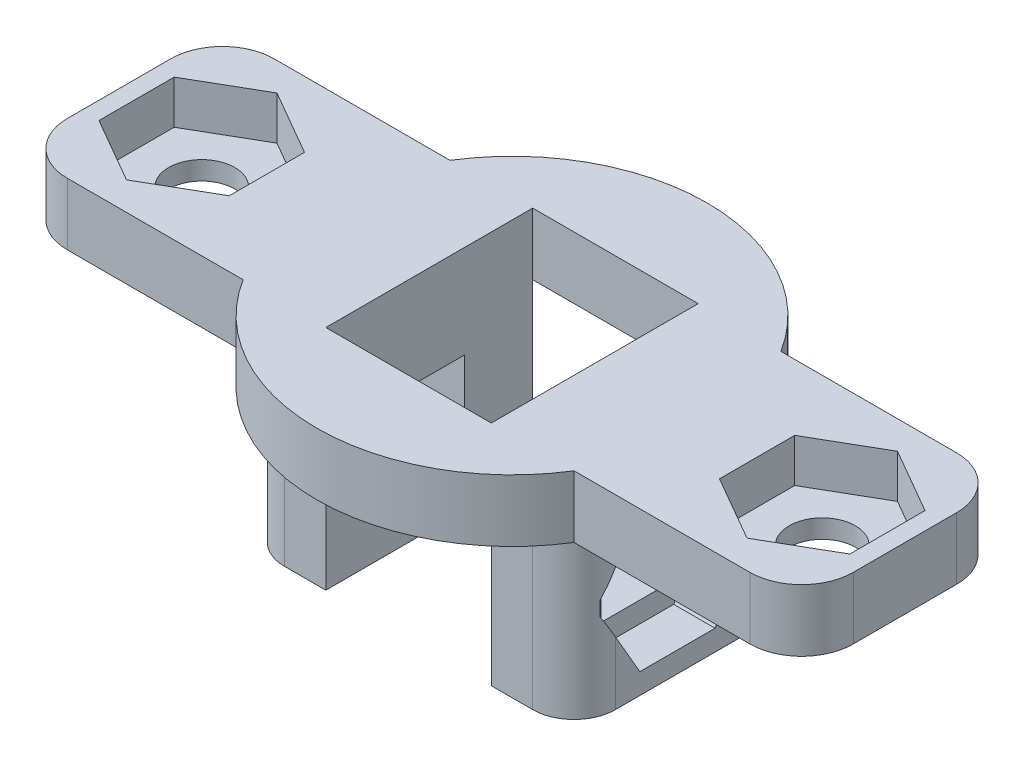
SolidWorks part; units mm, degrees
ref_plane "Front Plane" through (0, 0, 0) normal (0, 0, 1) x (1, 0, 0)
ref_plane "Top Plane" through (0, 0, 0) normal (0, 1, 0) x (1, 0, 0)
ref_plane "Right Plane" through (0, 0, 0) normal (1, 0, 0) x (0, 0, -1)
sketch "Sketch1" plane through (0, 0, 0) normal (0, 1, 0) x (1, 0, 0)
  line L0 (-19, 10) -> (-19, 0) construction
  line L1 (-38, 10) -> (0, 10)
  line L2 (-38, 10) -> (-38, 0)
  line L3 (-38, 0) -> (0, 0)
  line L4 (0, 10) -> (0, 0)
  line L9 (-27, 10) -> (-23, 10)
  line L10 (-27, 10) -> (-27, 0)
  line L11 (-27, 0) -> (-23, 0)
  line L12 (-23, 10) -> (-23, 0)
  line L13 (-15, 10) -> (-11, 10)
  line L14 (-15, 10) -> (-15, 0)
  line L15 (-15, 0) -> (-11, 0)
  line L16 (-11, 10) -> (-11, 0)
  line L17 (-32.5, 9) -> (-32.5, 10) construction
  line L18 (-38, 9) -> (-27, 9)
  line L19 (-38, 9) -> (-38, 1)
  line L20 (-38, 1) -> (-27, 1)
  line L21 (-27, 9) -> (-27, 1)
  line L22 (-32.5, 1) -> (-32.5, 0) construction
  arc A0 (-27, 0) -> (-11, 0) centre (-19, 5) ccw
  arc A1 (-11, 10) -> (-27, 10) centre (-19, 5) ccw
  dimension "D1" = 4
  dimension "D2" = 4
  dimension "D3" = 4
  dimension "D4" = 38
  dimension "D5" = 10
  dimension "D6" = 4
  dimension "D7" = 8
extrude "Boss-Extrude1" add sketch "Sketch1" along normal blind 3 contours L2 L20 L10 L18 | L12 L1 L10 L3 | L1 A1 | L16 L1 L14 L3 | L3 A0 | L1 L16 L3 L4 | L2 L18 L10 L1 | L20 L2 L3 L10 region at (-32.5, 0, -9.5) region at (-19, 0, -11.815) region at (-25, 0, -5) region at (-32.5, 0, -5) region at (-13, 0, -5) region at (-5.5, 0, -5) region at (-32.5, 0, -0.5) region at (-19, 0, 1.815)
extrude "Boss-Extrude2" add sketch "Sketch1<3>" against normal blind 8 contours L12 L1 L10 L3 | L16 L1 L14 L3 region at (-25, 0, -5) region at (-13, 0, -5)
sketch "Sketch1<3>" plane through (0, 0, 0) normal (0, 1, 0) x (1, 0, 0) same geometry as "Sketch1"
sketch "Sketch3" plane through (0, 3, 0) normal (0, 1, 0) x (1, 0, 0)
  line L0 (-38, 5) -> (0, 5) construction
  line L1 (-38, 10) -> (-38, 0) construction
  line L2 (0, 10) -> (0, 0) construction
  line L3 (-38, 10) -> (-38, 0) construction
  line L4 (-7.15, 6.8187) -> (-7.15, 3.1813)
  line L5 (-7.15, 3.1813) -> (-4, 1.3627)
  line L6 (-4, 1.3627) -> (-0.85, 3.1813)
  line L7 (-0.85, 3.1813) -> (-0.85, 6.8187)
  line L8 (-0.85, 6.8187) -> (-4, 8.6373)
  line L9 (-4, 8.6373) -> (-7.15, 6.8187)
  line L10 (-30.85, 3.1813) -> (-30.85, 6.8187)
  line L11 (-30.85, 6.8187) -> (-34, 8.6373)
  line L12 (-34, 8.6373) -> (-37.15, 6.8187)
  line L13 (-37.15, 6.8187) -> (-37.15, 3.1813)
  line L14 (-37.15, 3.1813) -> (-34, 1.3627)
  line L15 (-34, 1.3627) -> (-30.85, 3.1813)
  circle A0 centre (-4, 5) radius 3.15 construction
  circle A1 centre (-34, 5) radius 3.15 construction
  point P0 (-34, 5)
  point P1 (-4, 5)
  point P12 (-19, 5)
  dimension "D3" = 6.3
  dimension "D4" = 6.3
  dimension "D1" = 15
  dimension "D2" = 15
extrude "Cut-Extrude5" cut sketch "Sketch3" against normal blind 2.1
hole_wizard "Hole1" positions "3DSketch1" profile "Sketch8" legacy end condition through all
sketch3d "3DSketch1"
  point P0 (-4, 3, -5)
  point P3 (-34, 3, -5)
sketch "Sketch8" plane through (-4, 3, -5) normal (1, 0, 0) x (0, 0, 1)
  line L0 (0, 0) -> (0, 11)
  line L1 (0, 11) -> (1.6, 11)
  line L2 (1.6, 11) -> (1.6, 0)
  line L3 (1.6, 0) -> (0, 0)
  line L4 (0, 110) -> (0, -10) construction
  dimension "Diameter" = 3.2
  dimension "Depth" = 11
sketch "Sketch5" plane through (-27, 0, 0) normal (-1, 0, 0) x (0, 0, 1)
  line L0 (-5, 0) -> (-5, -8) construction
  line L1 (-6.7, -1.5) -> (-3.3, -1.5)
  line L2 (-6.7, -1.5) -> (-6.7, -6)
  line L3 (-6.7, -6) -> (-3.3, -6)
  line L4 (-3.3, -1.5) -> (-3.3, -6)
  line L6 (-10, -8) -> (0, -8) construction
  line L7 (-10, 0) -> (0, 0) construction
  line L8 (-7.7, -0.5) -> (-2.3, -0.5)
  line L9 (-7.7, -0.5) -> (-7.7, -7)
  line L10 (-7.7, -7) -> (-2.3, -7)
  line L11 (-2.3, -0.5) -> (-2.3, -7)
  point P10 (-5, -1.5)
  dimension "D1" = 3.4
  dimension "D2" = 4.5
  dimension "D3" = 1.5
  dimension "D4" = 1
  dimension "D5" = 1
  dimension "D6" = 1
  dimension "D7" = 1
extrude "Cut-Extrude1" cut sketch "Sketch5" against normal up to surface (4 mm away) contours L2 L1 L4 L3 up to face at (-23, -1.6667, -5)
extrude "Cut-Extrude4" cut sketch "Sketch5<4>" against normal blind 1 contours L0 L8 L9 L10 L3 L2 L1 | L8 L0 L1 L4 L3 L10 L11 region at (-27, -3.75, -3.2636) region at (-27, -3.75, -6.7364)
sketch "Sketch5<4>" plane through (-27, 0, 0) normal (-1, 0, 0) x (0, 0, 1) same geometry as "Sketch5"
sketch "Sketch6" plane through (-11, 0, 0) normal (1, 0, 0) x (0, 0, -1)
  line L0 (10, -8) -> (0, -8) construction
  line L1 (6.8187, -6.3) -> (8.6373, -3.15)
  line L2 (8.6373, -3.15) -> (6.8187, 0)
  line L3 (6.8187, 0) -> (3.1813, 0)
  line L4 (3.1813, 0) -> (1.3627, -3.15)
  line L5 (1.3627, -3.15) -> (3.1813, -6.3)
  line L6 (3.1813, -6.3) -> (6.8187, -6.3)
  line L7 (10, 0) -> (0, 0) construction
  line L8 (1.3627, -3.15) -> (1.3627, -3.85)
  line L10 (8.6373, -3.85) -> (8.6373, -3.15)
  line L11 (6.7, -6) -> (3.3, -6) construction
  line L12 (3.1813, -7) -> (6.8187, -7)
  line L13 (6.8187, -7) -> (8.6373, -3.85)
  line L14 (8.6373, -3.85) -> (6.8187, -0.7)
  line L15 (6.8187, -0.7) -> (3.1813, -0.7)
  line L16 (3.1813, -0.7) -> (1.3627, -3.85)
  line L17 (1.3627, -3.85) -> (3.1813, -7)
  line L18 (5, 0) -> (5, -8) construction
  line L19 (3.3, -1.5) -> (6.7, -1.5) construction
  line L20 (6.7, -1.5) -> (6.7, -6) construction
  line L21 (3.3, -6) -> (3.3, -1.5) construction
  line L22 (6.7, -6) -> (3.3, -6)
  line L23 (3.3, -1.5) -> (6.7, -1.5)
  line L24 (6.7, -1.5) -> (6.7, -6)
  line L25 (3.3, -6) -> (3.3, -1.5)
  circle A0 centre (5, -3.15) radius 3.15 construction
  circle A1 centre (5, -3.85) radius 3.15 construction
  point P24 (5, 0)
  line M14 (10, 0) -> (0, 0)
  dimension "D1" = 6.3
  dimension "D2" = 1
extrude "Cut-Extrude2" cut sketch "Sketch6" against normal blind 2 contours L22 L25 L6 L5 L16 L17 L12 L13 L14 L1 L24 | L15 L25 L23 L24 L14 L1 L2 L4 L5 L16 M14 | L16 L5 L8 | L14 L10 L1 | L15 L24 L6 L1 L14 | L6 L25 L15 L16 L5 region at (-11, -6.2114, -5) region at (-11, -4.9404, -7.6969) region at (-11, -2.0596, -7.6969) region at (-11, -3.5, -8.5699) region at (-11, -3.5, -1.4301)
extrude "Cut-Extrude3" cut sketch "Sketch6<3>" against normal through all contours L25 L23 L24 L22
sketch "Sketch6<3>" plane through (-11, 0, 0) normal (1, 0, 0) x (0, 0, -1) same geometry as "Sketch6"
fillet "Fillet1" radius 2.5 4 edges at (0, 1.5, -10) (0, 1.5, 0) (-38, 1.5, 0) (-38, 1.5, -10)
fillet "Fillet2" radius 2 4 edges at (-11, -4, 0) (-11, -4, -10) (-27, -4, -10) (-27, -4, 0)
